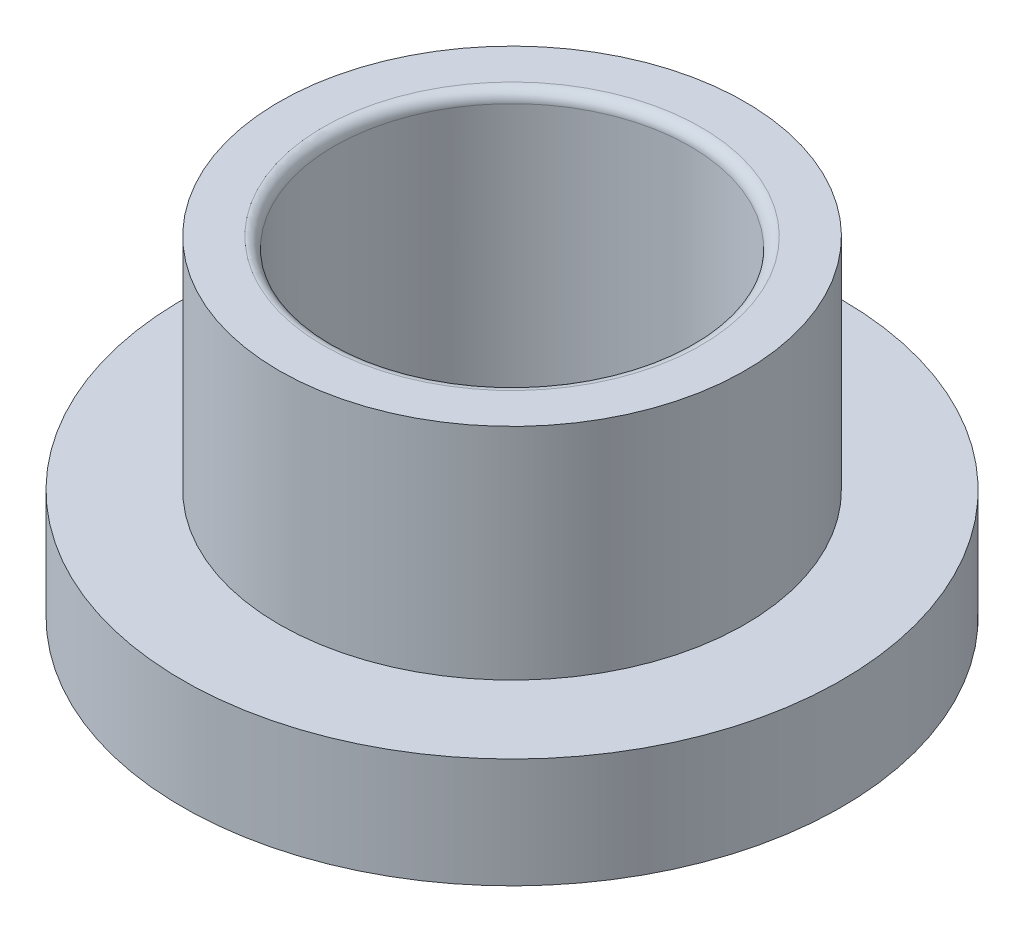
SolidWorks part; units mm, degrees
ref_plane "Front Plane" through (0, 0, 0) normal (0, 0, 1) x (1, 0, 0)
ref_plane "Top Plane" through (0, 0, 0) normal (0, 1, 0) x (1, 0, 0)
ref_plane "Right Plane" through (0, 0, 0) normal (1, 0, 0) x (0, 0, -1)
sketch "Sketch1" plane through (0, 0, 0) normal (0, 1, 0) x (1, 0, 0)
  circle A0 centre (0, 0) radius 16.2
  circle A1 centre (0, 0) radius 21.2
  dimension "D1" = 32.4
  dimension "D2" = 5
extrude "Boss-Extrude1" add sketch "Sketch1" along normal blind 20
fillet "Fillet1" radius 1 1 edges at (0, 20, 16.2)
sketch "Sketch2" plane through (0, 0, 0) normal (0, -1, 0) x (1, 0, 0)
  circle A0 centre (0, 0) radius 16.2 construction
  circle A1 centre (0, 0) radius 16.2
  circle A2 centre (0, 0) radius 30
  dimension "D1" = 60
extrude "Boss-Extrude2" add sketch "Sketch2" along normal blind 10
